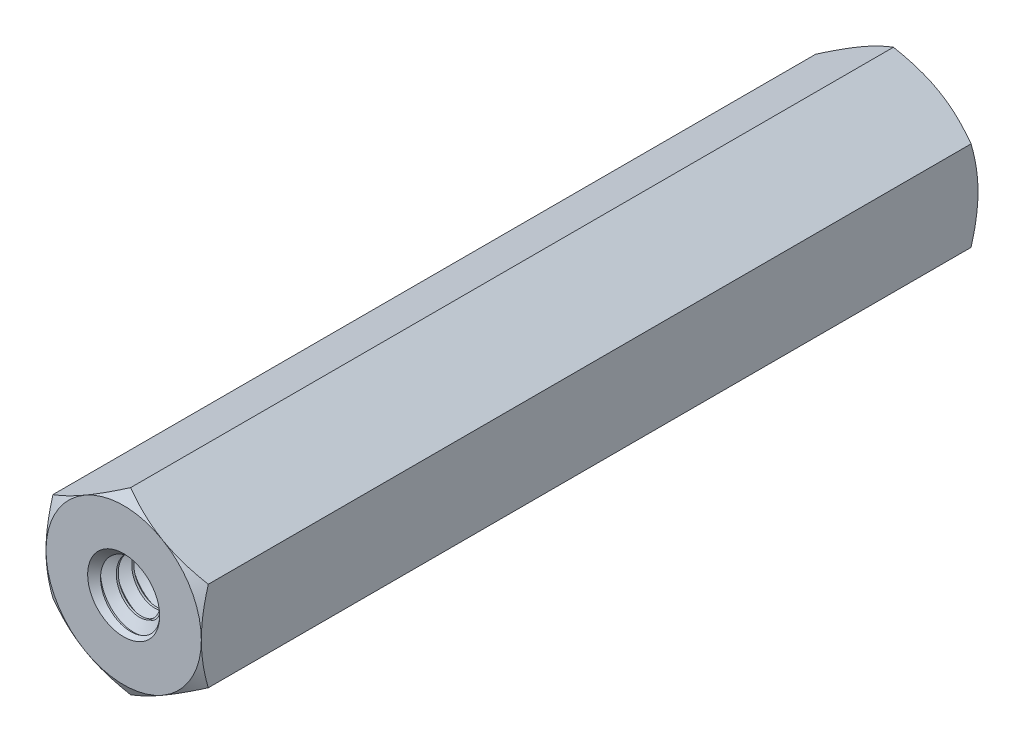
SolidWorks part; units mm, degrees
ref_plane "Front Plane" through (0, 0, 0) normal (0, 0, 1) x (1, 0, 0)
ref_plane "Top Plane" through (0, 0, 0) normal (0, 1, 0) x (1, 0, 0)
ref_plane "Right Plane" through (0, 0, 0) normal (1, 0, 0) x (0, 0, -1)
sketch "Sketch3" plane through (0, 0, 0) normal (1, 0, 0) x (0, 0, -1)
  line L0 (-15.875, 0) -> (15.875, 0) construction
  line L1 (0, 3.175) -> (0, -3.175) construction
  line L2 (-15.875, 1.4224) -> (-15.875, -1.4224) construction
  point P2 (9.525, 0)
  point P3 (-9.525, 0)
  dimension "D1" = 6.35
  dimension "Length" = 31.75
  dimension "Min Thread Length" = 6.35
  dimension "Thread Dia" = 2.8448
  dimension "Hex" = 6.35
sketch "Sketch1" plane through (0, 0, 0) normal (0, 0, 1) x (1, 0, 0)
  line L1 (0, 3.6662) -> (-3.175, 1.8331)
  line L2 (-3.175, 1.8331) -> (-3.175, -1.8331)
  line L3 (-3.175, -1.8331) -> (0, -3.6662)
  line L4 (0, -3.6662) -> (3.175, -1.8331)
  line L5 (3.175, -1.8331) -> (3.175, 1.8331)
  line L6 (3.175, 1.8331) -> (0, 3.6662)
  circle A0 centre (0, 0) radius 3.175 construction
  circle A1 centre (0, 0) radius 1.4224
extrude "Extrude1" add sketch "Sketch1" along normal up to vertex (15.875 mm away) and the other way up to vertex (15.875 mm away) up to point (0, 0, 15.875) other way up to point (0, 0, -15.875)
sketch "Sketch11" plane through (0, 0, -15.875) normal (0, 0, -1) x (-1, 0, 0)
  circle A0 centre (0, 0) radius 1.4224 construction
  circle A1 centre (0, 0) radius 1.4224
curve "Helix/Spiral1" pitch 0.635 height 32.385 radius 1.4224 centre (0, 0, -15.875) axis (0, 0, 1) start towards (0, 1, 0) parameters "Pitch"=0.635
sketch "Sketch12" plane through (0, 0, 0) normal (1, 0, 0) x (0, 0, -1)
  line L0 (16.4306, 1.4224) -> (15.875, 1.4224)
  line L1 (16.4306, 1.4224) -> (16.1925, 1.01)
  line L2 (16.1925, 1.01) -> (16.1131, 1.01)
  line L3 (16.1131, 1.01) -> (15.875, 1.4224)
  line L4 (16.1528, 1.01) -> (16.1528, 1.4224) construction
  line L5 (16.3116, 1.2162) -> (15.9941, 1.2162) construction
  dimension "D1" = 0.0794
  dimension "D2" = 0.3175
  dimension "D3" = 60
sweep "Sweep1" add profiles "Sketch12" path "Helix/Spiral1"
sketch "Sketch6" plane through (0, 0, -15.875) normal (0, 0, -1) x (-1, 0, 0)
  line L6 (0, 3.6662) -> (-3.175, 1.8331)
  line L7 (-3.175, 1.8331) -> (-3.175, -1.8331)
  line L8 (-3.175, -1.8331) -> (0, -3.6662)
  line L9 (0, -3.6662) -> (3.175, -1.8331)
  line L10 (3.175, -1.8331) -> (3.175, 1.8331)
  line L11 (3.175, 1.8331) -> (0, 3.6662)
  line L12 (0, 3.6662) -> (-3.175, 1.8331)
  line L13 (-3.175, 1.8331) -> (-3.175, -1.8331)
  line L14 (-3.175, -1.8331) -> (0, -3.6662)
  line L15 (0, -3.6662) -> (3.175, -1.8331)
  line L16 (3.175, -1.8331) -> (3.175, 1.8331)
  line L17 (3.175, 1.8331) -> (0, 3.6662)
  dimension "D1" = 0
extrude "Extrude2" cut sketch "Sketch6" along normal through all
sketch "Sketch7" plane through (0, 0, -15.875) normal (0, 0, -1) x (-1, 0, 0)
  circle A2 centre (0, 0) radius 1.4732
  circle A3 centre (0, 0) radius 1.4732
  dimension "D1" = 0.0508
extrude "Extrude3" cut sketch "Sketch7" against normal through all draft 43
sketch "Sketch8" plane through (0, 0, -15.875) normal (0, 0, -1) x (-1, 0, 0)
  circle A0 centre (0, 0) radius 3.175 construction
  circle A1 centre (0, 0) radius 3.175
extrude "Extrude4" cut sketch "Sketch8" against normal through all draft 60 flip side to cut
mirror "Mirror1" about plane through (0, 0, 0) normal (0, 0, 1) of "Extrude2", "Extrude3", "Extrude4"
sketch "Sketch9" plane through (0, 0, 0) normal (1, 0, 0) x (0, 0, -1)
  line L1 (-9.525, 1.4732) -> (9.525, 1.4732)
  line L2 (-9.525, 1.4732) -> (-9.525, 0)
  line L3 (-9.525, 0) -> (9.525, 0)
  line L4 (9.525, 1.4732) -> (9.525, 0)
  line L7 (-15.875, 0) -> (15.875, 0) construction
revolve "Revolve" add sketch "Sketch9" angle 360 about L0
sketch "Sketch10" plane through (0, 0, 0) normal (1, 0, 0) x (0, 0, -1)
  line L0 (15.875, 1.4224) -> (9.525, 1.4224)
  line L1 (-15.875, 1.4224) -> (-9.525, 1.4224)
  line L2 (9.525, 1.4224) -> (9.525, -1.4224)
  line L3 (-15.875, -1.4732) -> (-9.525, -1.4732)
  line L4 (-9.525, 1.4224) -> (-9.525, -1.4732)
  line L5 (9.525, -1.4224) -> (15.875, -1.4224)
equation "\"D1@Sketch3\" = \"Min Thread Length@Sketch3\""
equation "\"D3@Helix/Spiral1\" = \"Length@Sketch3\"+\"Pitch@Helix/Spiral1\""
equation "\"D1@Sketch12\" = \"Pitch@Helix/Spiral1\"*.125"
equation "\"D2@Sketch12\" = \"Pitch@Helix/Spiral1\"*.5"
